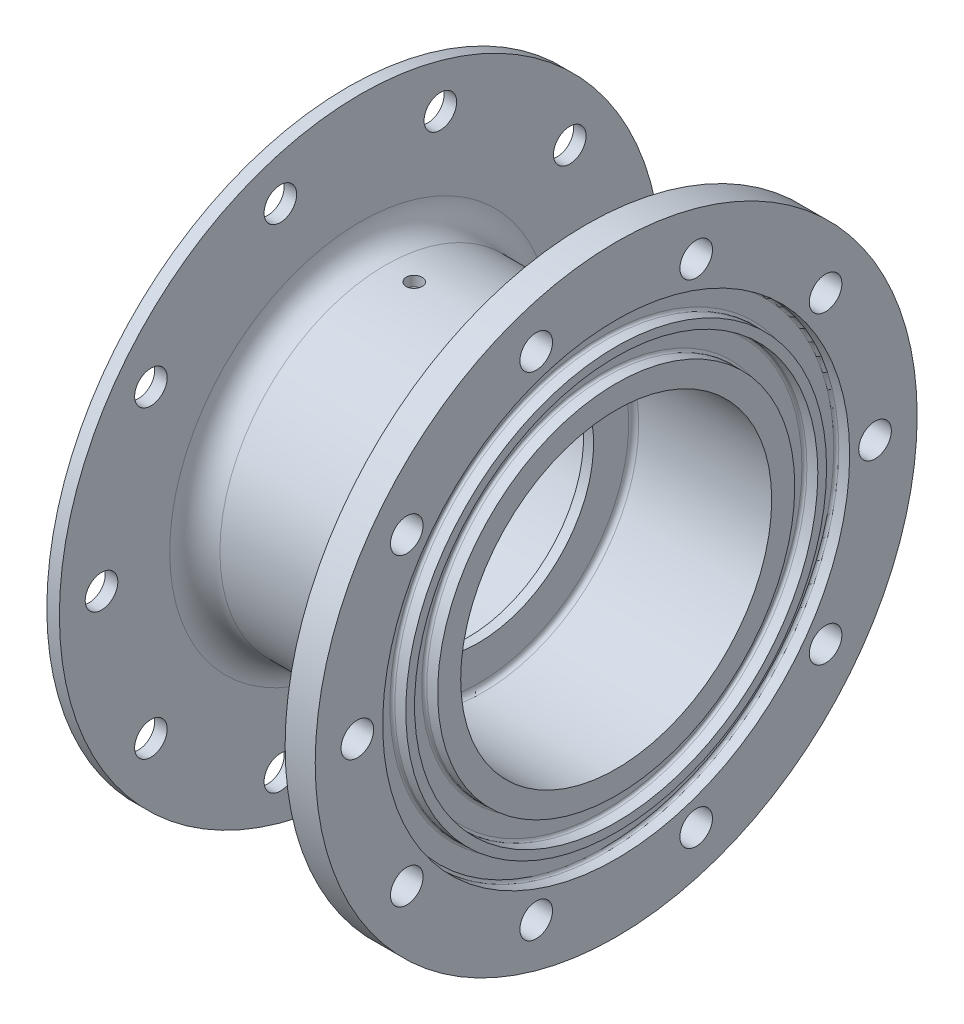
SolidWorks part; units mm, degrees
material "AISI 321 Annealed Stainless Steel (SS)"
ref_plane "Front Plane" through (0, 0, 0) normal (0, 0, 1) x (1, 0, 0)
ref_plane "Top Plane" through (0, 0, 0) normal (0, 1, 0) x (1, 0, 0)
ref_plane "Right Plane" through (0, 0, 0) normal (1, 0, 0) x (0, 0, -1)
sketch "Sketch1" plane through (0, 0, 0) normal (0, 0, 1) x (1, 0, 0)
  line L0 (-117.5079, 0) -> (156.4607, 0) construction
  line L1 (-1, -23) -> (-1, -30)
  line L2 (-11.75, -6.8094) -> (-11.75, -76.6455) construction
  line L3 (1, -23) -> (1, -30)
  line L4 (1, -31) -> (25, -31) construction
  line L5 (25, -31) -> (25, -60) construction
  line L6 (25, -60) -> (22.5, -60)
  line L7 (22.5, -60) -> (22.5, -38)
  line L8 (17.5, -33) -> (-17.5, -33)
  line L9 (-22.5, -38) -> (-22.5, -60)
  line L10 (-22.5, -60) -> (-25, -60)
  line L11 (-25, -60) -> (-25, -31) construction
  line L12 (-25, -31) -> (-1, -31) construction
  line L13 (-1, -23) -> (1, -23)
  line L14 (0, -6.8094) -> (0, -76.6455) construction
  line L15 (-25, -60) -> (-25, -31)
  line L16 (25, -60) -> (25, -31) construction
  line L17 (25, -31) -> (28.5, -31)
  line L18 (28.5, -31) -> (28.5, -60)
  line L19 (-25, -31) -> (-2, -31)
  line L20 (28.5, -60) -> (25, -60)
  line L22 (25, -31) -> (2, -31)
  arc A0 (-22.5, -38) -> (-17.5, -33) centre (-17.5, -38) cw
  arc A1 (22.5, -38) -> (17.5, -33) centre (17.5, -38) ccw
  arc A2 (-1, -30) -> (-2, -31) centre (-2, -30) cw
  arc A3 (2, -31) -> (1, -30) centre (2, -30) cw
  dimension "D5" = 5
  dimension "D6" = 5
  dimension "D9" = 1
  dimension "D10" = 1
  dimension "Inner Radius" = 31
  dimension "D1" = 31
  dimension "Baffle Height" = 8
  dimension "Wall Thickness" = 2
  dimension "Forward Flange Thickness" = 2.5
  dimension "Aft Flange Thickness" = 2.5
  dimension "Baffle Thickness" = 2
  dimension "Catalyst Bed Length" = 50
  dimension "D2" = 24
  dimension "D3" = 1
  dimension "Forward Flange Outer Radius" = 60
  dimension "Aft Flange Outer Radius" = 60
  dimension "D4" = 10.75
  dimension "D7" = 3.5
revolve "Revolve9" add sketch "Sketch1" angle 360 about L0
sketch "Sketch3" plane through (-25, 0, 0) normal (-1, 0, 0) x (0, 0, 1)
  line L0 (0, 0) -> (-15.9453, -49.0745) construction
  line L1 (0, -6.8094) -> (0, -76.6455) construction
  circle A0 centre (-15.9453, -49.0745) radius 3.25
  dimension "D1" = 51.6
  dimension "D2" = 18
  dimension "Forward Flange Hole Diameter" = 6.5
extrude "Cut-Extrude3" cut sketch "Sketch3" against normal through all
pattern_circular "CirPattern1" count 10 over 360 of "Cut-Extrude3"
ref_axis "Axis1" through (28.5, 0, 0) along (-1, 0, 0)
hole_wizard "Ø3.2 (3.2) Diameter Hole1" positions "3DSketch1" profile "Sketch7" hole size "Ø3.2" standard "BSI"
sketch3d "3DSketch1"
  line L0 (-11.75, -6.8094, 0) -> (-11.75, -76.6455, 0) construction
  point P0 (-11.75, 33, 0)
sketch "Sketch7" plane through (-11.75, 33, 0) normal (1, 0, 0) x (0, 0, 1)
  line L0 (0, 0) -> (0, 5.9614)
  line L1 (0, 5.9614) -> (1.6, 5)
  line L2 (1.6, 5) -> (1.6, 0)
  line L5 (1.6, 0) -> (0, 0)
  line L10 (0, 5.9614) -> (-1.6, 5) construction
  line L11 (0, -6.35) -> (0, 107.95) construction
  dimension "Hole Dia." = 3.2
  dimension "Hole Depth" = 5
  dimension "Drill Angle" = 118
ref_plane "Plane1" through (-25, 0, 0) normal (0, -1, 0) x (0, 0, 1)
ref_plane "Plane2" through (25, 0, 0) normal (0, -1, 0) x (0, 0, -1)
ref_plane "Plane3" through (25, 0, 0) normal (0, -1, 0) x (0, 0, -1)
ref_plane "Plane4" through (25, 0, 0) normal (0, -1, 0) x (0, 0, -1)
ref_plane "Plane5" through (25, 0, 0) normal (0, -1, 0) x (0, 0, -1)
ref_plane "Plane6" through (25, 0, 0) normal (0, -1, 0) x (0, 0, -1)
sketch "Sketch8" plane through (0, 0, 0) normal (0, 0, 1) x (1, 0, 0)
  line L0 (28.5, -60) -> (28.5, 60) construction
  line L1 (28.5, 40.195) -> (26.33, 40.195)
  line L2 (25.83, 39.695) -> (25.83, 36.095)
  line L3 (26.33, 35.595) -> (28.5, 35.595)
  line L4 (28.5, 35.595) -> (28.5, 40.195)
  line L5 (28.5, 41.945) -> (26.33, 41.945)
  line L6 (25.83, 42.445) -> (25.83, 46.045)
  line L7 (26.33, 46.545) -> (28.5, 46.545)
  line L8 (28.5, 45.8245) -> (28.5, 52.3245) construction
  line L9 (28.5, 46.545) -> (28.5, 41.945)
  arc A0 (25.83, 36.095) -> (26.33, 35.595) centre (26.33, 36.095) ccw
  arc A1 (25.83, 39.695) -> (26.33, 40.195) centre (26.33, 39.695) cw
  arc A2 (25.83, 42.445) -> (26.33, 41.945) centre (26.33, 42.445) ccw
  arc A3 (25.83, 46.045) -> (26.33, 46.545) centre (26.33, 46.045) cw
  point P0 (28.5, 37.895)
  point P1 (28.5, 44.245)
  point P17 (25.83, 35.595)
  point P20 (25.83, 40.195)
  point P25 (25.83, 46.545)
  dimension "D9" = 0.5
  dimension "D10" = 0.5
  dimension "D11" = 0.5
  dimension "D12" = 0.5
  dimension "D1" = 37.895
  dimension "D2" = 44.245
  dimension "D3" = 4.6
  dimension "D4" = 2.3
  dimension "D5" = 2.67
  dimension "D6" = 2.67
  dimension "D7" = 4.6
  dimension "D8" = 2.3
revolve "Cut-Revolve1" cut sketch "Sketch8" angle 360 about axis through (28.5, 0, 0) along (-1, 0, 0)
equation "\"D1@Sketch1\"=\"Inner Radius@Sketch1\""
equation "\"D2@Sketch1\"=(\"Catalyst Bed Length@Sketch1\"/2)-(\"Baffle Thickness@Sketch1\"/2)"
equation "\"D3@Sketch1\"=\"Baffle Thickness@Sketch1\"/2"
equation "\"Aft Flange Outer Radius@Sketch1\"=\"Forward Flange Outer Radius@Sketch1\""
equation "\"D1@Cut-Extrude3\"=\"Forward Flange Thickness@Sketch1\""
equation "\"D4@Sketch1\"=21.5/2"
equation "\"D7@Sketch1\"=6-2.5"
equation "\"D1@Sketch8\"=75.79/2"
equation "\"D2@Sketch8\"=88.49/2"
